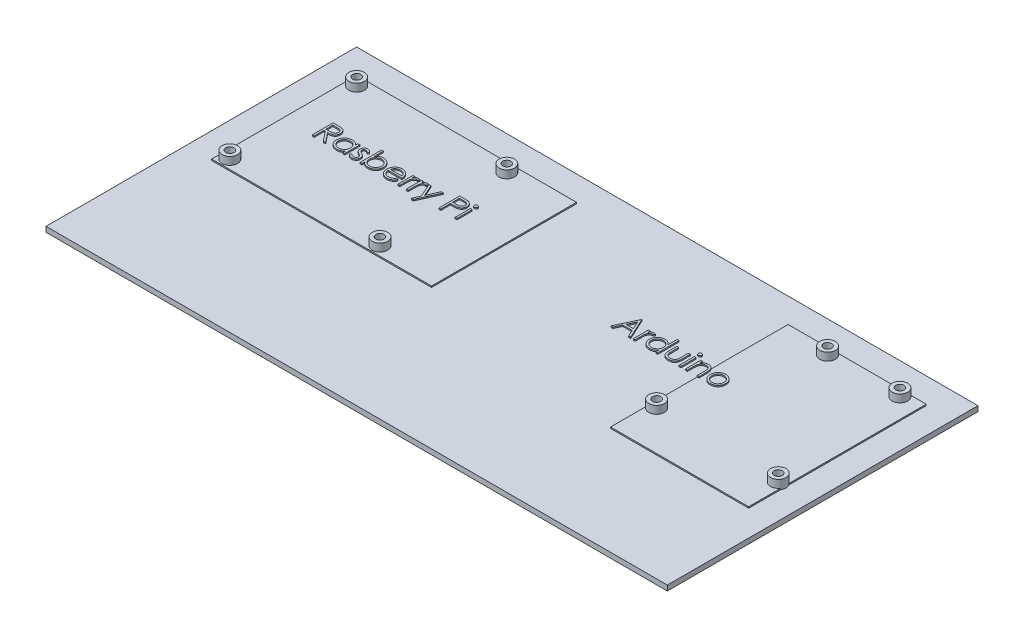
SolidWorks part; units mm, degrees
ref_plane "Front Plane" through (0, 0, 0) normal (0, 0, 1) x (1, 0, 0)
ref_plane "Top Plane" through (0, 0, 0) normal (0, 1, 0) x (1, 0, 0)
ref_plane "Right Plane" through (0, 0, 0) normal (1, 0, 0) x (0, 0, -1)
sketch "Sketch1" plane through (0, 0, 0) normal (0, 1, 0) x (1, 0, 0)
  line L1 (-80.6991, 57.4337) -> (159.3009, 57.4337)
  line L2 (-80.6991, 57.4337) -> (-80.6991, -62.5663)
  line L3 (-80.6991, -62.5663) -> (159.3009, -62.5663)
  line L4 (159.3009, 57.4337) -> (159.3009, -62.5663)
  dimension "D1" = 240
  dimension "D2" = 120
extrude "Boss-Extrude1" add sketch "Sketch1" along normal blind 2
sketch "Sketch2" plane through (0, 2, 0) normal (0, 1, 0) x (1, 0, 0)
  line L0 (159.3009, -62.5663) -> (159.3009, 57.4337) construction
  line L1 (95.9609, 47.4337) -> (149.3009, 47.4337)
  line L2 (95.9609, 47.4337) -> (95.9609, -21.1463)
  line L3 (95.9609, -21.1463) -> (149.3009, -21.1463)
  line L4 (149.3009, 47.4337) -> (149.3009, -21.1463)
  line L5 (159.3009, 57.4337) -> (-80.6991, 57.4337) construction
  dimension "D1" = 53.34
  dimension "D2" = 68.58
  dimension "D3" = 10
  dimension "D4" = 10
extrude "Boss-Extrude2" add sketch "Sketch2" along normal blind 0.5
sketch "Sketch4" plane through (0, 2.5, 0) normal (0, 1, 0) x (1, 0, 0)
  line L0 (149.3009, 47.4337) -> (95.9609, 47.4337) construction
  line L1 (149.3009, -21.1463) -> (149.3009, 47.4337) construction
  line L2 (95.9609, 47.4337) -> (95.9609, -21.1463) construction
  line L3 (149.3009, -21.1463) -> (149.3009, 47.4337) construction
  line L4 (95.9609, -21.1463) -> (149.3009, -21.1463) construction
  circle A0 centre (141.6809, 44.8937) radius 1.5875
  circle A1 centre (113.7409, 44.8937) radius 1.5875
  circle A2 centre (146.7609, -7.1763) radius 1.5875
  circle A3 centre (98.5009, -5.9063) radius 1.5875
  circle A4 centre (146.7609, -7.1763) radius 3
  circle A5 centre (98.5009, -5.9063) radius 3
  circle A6 centre (113.7409, 44.8937) radius 3
  circle A7 centre (141.6809, 44.8937) radius 3
  dimension "D1" = 2.54
  dimension "D3" = 17.78
  dimension "D5" = 2.54
  dimension "D7" = 2.54
  dimension "D2" = 7.62
  dimension "D4" = 2.54
  dimension "D6" = 13.97
  dimension "D8" = 15.24
extrude "Boss-Extrude3" add sketch "Sketch4" along normal blind 3
extrude "Boss-Extrude4" add sketch "Sketch4<2>" against normal blind 0.5
sketch "Sketch4<2>" plane through (0, 2.5, 0) normal (0, 1, 0) x (1, 0, 0) same geometry as "Sketch4"
sketch "Sketch9" plane through (0, 2.5, 0) normal (0, 1, 0) x (1, 0, 0)
  text T0 "Arduino" font "Century Gothic" height 8
extrude "Boss-Extrude6" add sketch "Sketch9" along normal blind 0.5
sketch "Sketch11" plane through (0, 2, 0) normal (0, 1, 0) x (1, 0, 0)
  line L0 (-80.6991, 57.4337) -> (-80.6991, -62.5663) construction
  line L1 (-70.6991, 47.4337) -> (14.225, 47.4337)
  line L2 (-70.6991, 47.4337) -> (-70.6991, -8.5663)
  line L3 (-70.6991, -8.5663) -> (14.225, -8.5663)
  line L4 (14.225, 47.4337) -> (14.225, -8.5663)
  line L5 (159.3009, 57.4337) -> (-80.6991, 57.4337) construction
  dimension "D1" = 84.9241
  dimension "D2" = 56
  dimension "D3" = 10
  dimension "D4" = 10
extrude "Boss-Extrude7" add sketch "Sketch11" along normal blind 0.5
sketch "Sketch12" plane through (0, 2.5, 0) normal (0, 1, 0) x (1, 0, 0)
  text T0 "Rasberry Pi" font "Century Gothic" height 8
sketch "Sketch13" plane through (0, 2.5, 0) normal (0, 1, 0) x (1, 0, 0)
  line L0 (14.225, 47.4337) -> (-70.6991, 47.4337) construction
  line L1 (-70.6991, 47.4337) -> (-70.6991, -8.5663) construction
  line L2 (-70.6991, -8.5663) -> (14.225, -8.5663) construction
  circle A0 centre (-67.1991, 43.9337) radius 1.5875
  circle A1 centre (-67.1991, -5.0663) radius 1.5875
  circle A2 centre (-9.1991, 43.9337) radius 1.5875
  circle A3 centre (-9.1991, -5.0663) radius 1.5875
  circle A4 centre (-67.1991, 43.9337) radius 3
  circle A5 centre (-9.1991, 43.9337) radius 3
  circle A6 centre (-67.1991, -5.0663) radius 3
  circle A7 centre (-9.1991, -5.0663) radius 3
  dimension "D1" = 3.5
  dimension "D3" = 3.5
  dimension "D6" = 58
  dimension "D8" = 49
  dimension "D2" = 3.5
  dimension "D4" = 3.5
  dimension "D5" = 49
  dimension "D7" = 3.5
  dimension "D9" = 58
extrude "Boss-Extrude10" add sketch "Sketch13" along normal blind 3
extrude "Boss-Extrude11" add sketch "Sketch12" along normal blind 0.5
